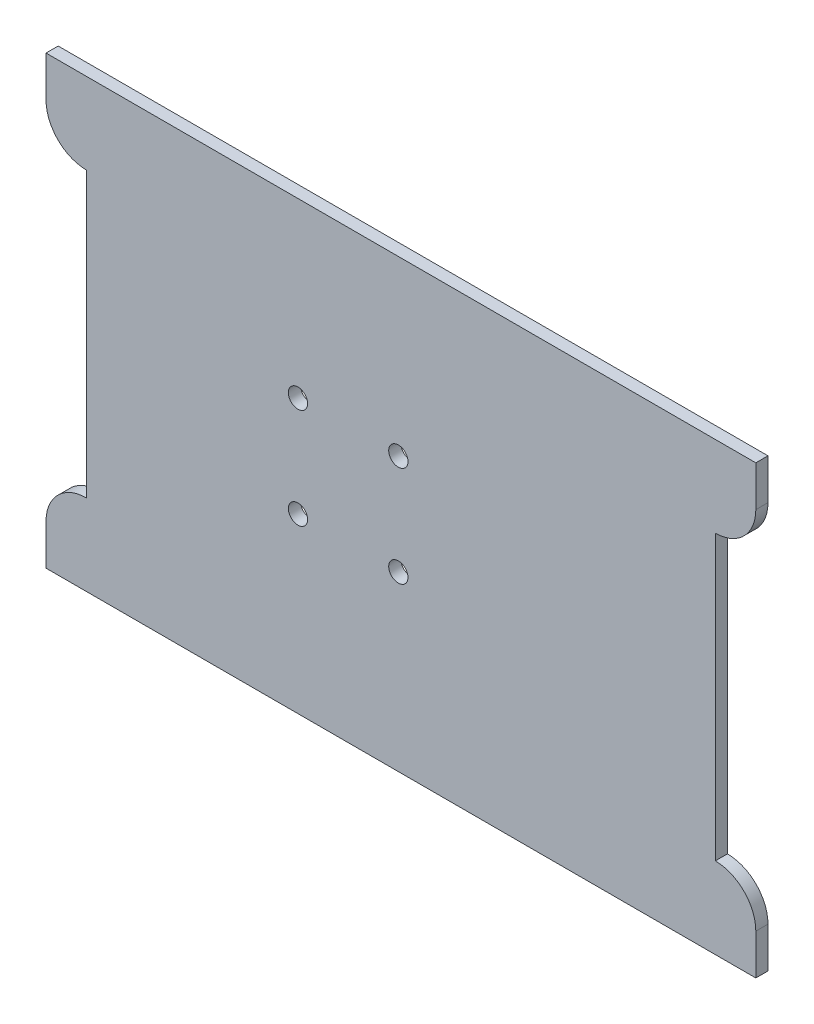
SolidWorks part; units mm, degrees
ref_plane "前视基准面" through (0, 0, 0) normal (0, 0, 1) x (1, 0, 0)
ref_plane "上视基准面" through (0, 0, 0) normal (0, 1, 0) x (1, 0, 0)
ref_plane "右视基准面" through (0, 0, 0) normal (1, 0, 0) x (0, 0, -1)
sketch "草图2" plane through (0, 0, 0) normal (0, 0, 1) x (1, 0, 0)
  line L1 (35, -22) -> (-35, -22)
  line L2 (35, -22) -> (35, 22)
  line L3 (35, 22) -> (-35, 22)
  line L4 (-35, -22) -> (-35, 22)
  line L5 (35, -22) -> (-35, 22) construction
  line L6 (35, 22) -> (-35, -22) construction
  point P0 (0, 0)
  dimension "D1" = 70
  dimension "D2" = 44
sheet metal parameters "钣金1" thickness 1.2 parameters "D1"=2, "厚度"=1.2
base flange "基体-法兰1" sketch "草图2" thickness 1.2 reverse thickness direction no parameters "D1"=2
sketch "草图5" plane through (0, 0, 0) normal (0, 0, 1) x (1, 0, 0)
  line L0 (35, -22) -> (35, 22) construction
  line L1 (39, -14) -> (35, -14)
  line L2 (39, -14) -> (39, 14)
  line L3 (39, 14) -> (35, 14)
  line L4 (31, -14) -> (31, 14)
  line L5 (39, -14) -> (31, 14) construction
  line L6 (39, 14) -> (31, -14) construction
  line L7 (0, 0) -> (48.9166, 0) construction
  line L8 (35, -22) -> (35, 22) construction
  line L9 (35, -18) -> (35, -14)
  line L10 (35, 14) -> (35, 18)
  line L11 (35, 22) -> (-35, 22) construction
  line L12 (0, 30.4992) -> (0, -25.6971) construction
  line L13 (-39, -14) -> (-39, 14)
  line L14 (-39, 14) -> (-35, 14)
  line L15 (-35, 14) -> (-35, 18)
  line L16 (-31, -14) -> (-31, 14)
  line L17 (-35, -18) -> (-35, -14)
  line L18 (-39, -14) -> (-35, -14)
  arc A0 (31, 14) -> (35, 18) centre (31, 18) ccw
  arc A1 (31, -14) -> (35, -18) centre (31, -18) cw
  arc A2 (-31, 14) -> (-35, 18) centre (-31, 18) cw
  arc A3 (-31, -14) -> (-35, -18) centre (-31, -18) ccw
  point P0 (35, 0)
  dimension "D1" = 4
  dimension "D2" = 8
extrude "切除-拉伸1" cut sketch "草图5" against normal through all normal cut yes
sketch "草图6" plane through (0, 0, 0) normal (0, 0, 1) x (1, 0, 0)
  line L0 (-38.1134, 0) -> (41.8496, 0) construction
  line L6 (9.5517, -14.7558) -> (-10.1538, 4.9497) construction
  circle A0 centre (-10.1538, 4.9497) radius 0.95
  circle A1 centre (-0.2543, 4.9497) radius 0.95
  circle A2 centre (-0.2543, -4.9497) radius 0.95
  circle A3 centre (-10.1538, -4.9497) radius 0.95
  point P3 (-5.2041, 0)
  point P18 (-5.2041, 0)
  dimension "D1" = 45
  dimension "D4" = 1.9
  dimension "D2" = 7
  dimension "D3" = 4
extrude "切除-拉伸2" cut sketch "草图6" against normal through all normal cut yes
flat pattern "平板型式1" [suppressed]
sketch "折弯-线1" plane through (0, 0, 0) normal (0, 1, 0) x (1, 0, 0)
sketch3d "边界框1" [suppressed]
  line L0 (-33, -20, 0) -> (33, -20, 0) construction
  line L1 (-33, 20, 0) -> (33, 20, 0) construction
  line L2 (-33, -20, 0) -> (-33, 20, 0) construction
  line L3 (33, -20, 0) -> (33, 20, 0) construction
